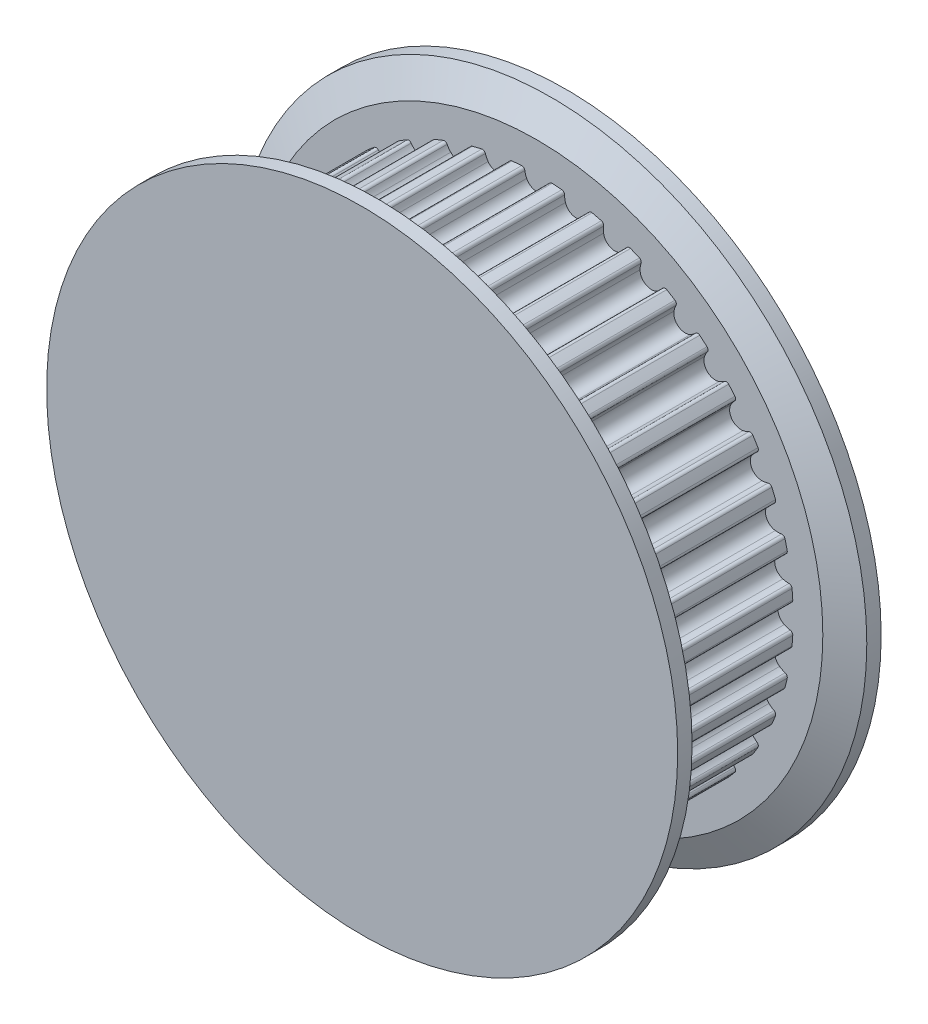
SolidWorks part; units mm, degrees
ref_plane "Front Plane" through (0, 0, 0) normal (0, 0, 1) x (1, 0, 0)
ref_plane "Top Plane" through (0, 0, 0) normal (0, 1, 0) x (1, 0, 0)
ref_plane "Right Plane" through (0, 0, 0) normal (1, 0, 0) x (0, 0, -1)
sketch "Sketch1" plane through (0, 0, 0) normal (0, 0, 1) x (1, 0, 0)
  line L1 (-1.8596, 11.734) -> (1.8596, 11.734) construction
  line L4 (0, 0) -> (0, 11.734) construction
  line L5 (0, 11.734) -> (0, 15.5209) construction
  line L6 (0, 12.738) -> (1.9938, 12.581) construction
  line L7 (1.9938, 12.581) -> (2.8408, 12.4468) construction
  line L8 (1.9938, 12.581) -> (1.8596, 11.734) construction
  line L9 (-1.9938, 12.581) -> (-1.8596, 11.734) construction
  line L10 (-1.9541, 12.3301) -> (-2.4354, 15.367)
  line L11 (-2.4354, 15.367) -> (2.4354, 15.367)
  line L12 (2.4354, 15.367) -> (1.9541, 12.3301)
  circle A0 centre (0, 0) radius 12.738 construction
  circle A1 centre (0, 0) radius 15.367 construction
  circle A2 centre (0, 0) radius 12.484 construction
  arc A3 (-0.4989, 12.0458) -> (0.4989, 12.0458) centre (0, 12.289) ccw
  arc A4 (-0.4989, 12.0458) -> (-0.5887, 12.3344) centre (0.4, 12.484) cw
  arc A5 (-1.9541, 12.3301) -> (-0.746, 12.4617) centre (0, 0) cw
  arc A6 (-0.5887, 12.3344) -> (-0.746, 12.4617) centre (-0.7371, 12.312) ccw
  arc A7 (1.9541, 12.3301) -> (0.746, 12.4617) centre (0, 0) ccw
  arc A8 (0.5887, 12.3344) -> (0.746, 12.4617) centre (0.7371, 12.312) cw
  arc A9 (0.4989, 12.0458) -> (0.5887, 12.3344) centre (-0.4, 12.484) ccw
  point P6 (0, 20.9083)
  point P11 (0, 12.738)
  point P13 (0, 15.367)
  point P14 (0, 12.484)
  dimension "D1" = 5.3874
  dimension "D2" = 2.7829
sketch "Sketch2" plane through (0, 0, 0) normal (1, 0, 0) x (0, 0, -1)
  line L0 (-9.1313, 3.175) -> (9.1313, 3.175)
  line L1 (-9.1313, 3.175) -> (-9.1313, 9.575)
  line L2 (-9.1313, 9.575) -> (-0.7787, 9.575)
  line L3 (-0.7787, 9.575) -> (-0.7787, 15.367)
  line L4 (-0.7787, 15.367) -> (0.6213, 15.367) construction
  line L5 (0.6213, 15.367) -> (0.6213, 12.484) construction
  line L6 (0.6213, 12.484) -> (7.7313, 12.484)
  line L7 (7.7313, 12.484) -> (7.7313, 15.367) construction
  line L8 (7.7313, 15.367) -> (9.1313, 15.367) construction
  line L9 (9.1313, 15.367) -> (9.1313, 3.175)
  line L10 (-9.1313, 0) -> (9.1313, 0) construction
  line L11 (8.4313, 15.367) -> (7.7313, 13.9255)
  line L12 (0.6213, 13.9255) -> (-0.0787, 15.367)
  line L13 (-0.7787, 15.367) -> (-0.0787, 15.367)
  line L14 (0.6213, 13.9255) -> (0.6213, 12.484)
  line L15 (7.7313, 12.484) -> (7.7313, 13.9255)
  line L16 (8.4313, 15.367) -> (9.1313, 15.367)
  arc A0 (0.6213, 13.9255) -> (-0.0787, 15.367) centre (-1.2129, 13.9255) ccw construction
  arc A1 (7.7313, 13.9255) -> (8.4313, 15.367) centre (9.5655, 13.9255) cw construction
  point P12 (0.6213, 13.9255)
  point P14 (-0.0787, 15.367)
  point P20 (7.7313, 13.9255)
  point P21 (8.4313, 15.367)
  point P25 (7.7313, 0)
  point P26 (0.6213, 0)
revolve "Revolve1" add sketch "Sketch2" angle 360 mid plane about L10
sketch "Sketch3" plane through (0, 0, 0) normal (0, 0, 1) x (1, 0, 0)
  line L6 (2.4354, 15.367) -> (-2.4354, 15.367)
  line L7 (1.9541, 12.3301) -> (2.4354, 15.367)
  line L8 (-2.4354, 15.367) -> (-1.9541, 12.3301)
  line L9 (2.4354, 15.367) -> (-2.4354, 15.367)
  line L10 (1.9541, 12.3301) -> (2.4354, 15.367)
  line L11 (-2.4354, 15.367) -> (-1.9541, 12.3301)
  arc A8 (1.9541, 12.3301) -> (0.746, 12.4617) centre (0, 0) ccw
  arc A9 (0.746, 12.4617) -> (0.5887, 12.3344) centre (0.7371, 12.312) ccw
  arc A10 (0.4989, 12.0458) -> (0.5887, 12.3344) centre (-0.4, 12.484) ccw
  arc A11 (-0.4989, 12.0458) -> (0.4989, 12.0458) centre (0, 12.289) ccw
  arc A12 (-0.5887, 12.3344) -> (-0.4989, 12.0458) centre (0.4, 12.484) ccw
  arc A13 (-0.5887, 12.3344) -> (-0.746, 12.4617) centre (-0.7371, 12.312) ccw
  arc A14 (-0.746, 12.4617) -> (-1.9541, 12.3301) centre (0, 0) ccw
  arc A15 (1.9541, 12.3301) -> (0.746, 12.4617) centre (0, 0) ccw
  arc A16 (0.746, 12.4617) -> (0.5887, 12.3344) centre (0.7371, 12.312) ccw
  arc A17 (0.4989, 12.0458) -> (0.5887, 12.3344) centre (-0.4, 12.484) ccw
  arc A18 (-0.4989, 12.0458) -> (0.4989, 12.0458) centre (0, 12.289) ccw
  arc A19 (-0.5887, 12.3344) -> (-0.4989, 12.0458) centre (0.4, 12.484) ccw
  arc A20 (-0.5887, 12.3344) -> (-0.746, 12.4617) centre (-0.7371, 12.312) ccw
  arc A21 (-0.746, 12.4617) -> (-1.9541, 12.3301) centre (0, 0) ccw
  dimension "D1" = 0
extrude "Cut-Extrude1" cut sketch "Sketch3" against normal up to vertex (7.7313 mm away) from vertex up to point (0, 12.484, -7.7313) starting at point (0, 12.484, -0.6213)
pattern_circular "CirPattern1" count 40 over 360 about axis through (0, 0, 9.1313) along (0, 0, 1) of "Cut-Extrude1"
sketch "Sketch4" plane through (0, 0, 0) normal (1, 0, 0) x (0, -1, 0)
  line L0 (0, -0.7787) -> (0, -9.1313) construction
  line L1 (-9.575, -0.7787) -> (9.575, -0.7787) construction
  line L2 (-9.575, -9.1313) -> (9.575, -9.1313) construction
  circle A0 centre (0, -4.955) radius 1.7526
extrude "Cut-Extrude2" cut sketch "Sketch4" along normal through all
ref_plane "Plane1" through (0, 0, 4.955) normal (0, 0, 1) x (1, 0, 0)
sketch "Sketch5" plane through (0, 0, 4.955) normal (0, 0, 1) x (1, 0, 0)
  line L0 (0, 0.1664) -> (0, 9.575) construction
  line L1 (3.175, -1.3716) -> (3.175, 0)
  line L2 (3.556, -1.7526) -> (9.0322, -1.7526)
  line L3 (3.175, 0) -> (9.575, 0) construction
  line L4 (3.175, 0) -> (9.4132, 0)
  line L5 (9.4132, 0) -> (9.4132, -1.3716)
  line L6 (3.556, -1.7526) -> (3.175, -1.3716)
  line L7 (9.4132, -1.3716) -> (9.0322, -1.7526)
  circle A0 centre (0, 0) radius 9.575 construction
  circle A1 centre (0, 0) radius 3.175 construction
  point P2 (3.175, -1.7526)
  point P11 (9.4132, -1.7526)
revolve "Revolve2" add sketch "Sketch5" angle 360 mid plane about L4
sketch "Sketch6" plane through (9.4132, 5.3841, 0) normal (-1, 0, 0) x (0, -1, 0)
  line L1 (5.3841, 5.9669) -> (4.5078, 5.4609)
  line L2 (4.5078, 5.4609) -> (4.5078, 4.4491)
  line L3 (4.5078, 4.4491) -> (5.3841, 3.9431)
  line L4 (5.3841, 3.9431) -> (6.2604, 4.4491)
  line L5 (6.2604, 4.4491) -> (6.2604, 5.4609)
  line L6 (6.2604, 5.4609) -> (5.3841, 5.9669)
  circle A0 centre (5.3841, 4.955) radius 0.8763 construction
  dimension "D1" = 1.7526
extrude "Cut-Extrude3" cut sketch "Sketch6" along normal blind 1.3144
pattern_circular "CirPattern2" count 2 over 90 about axis through (0, 0, 9.1313) along (0, 0, 1) of "Cut-Extrude2", "Revolve2", "Cut-Extrude3"
chamfer "Chamfer1" distance 0.4788 angle 45 2 edges at (3.175, 0, 9.1313) (9.575, 0, 9.1313)
ref_axis "Center Axis 1" through (0, 0, -9.1313) along (0, 0, 1)
ref_plane "Contact Plane 1" through (0, 0, 9.1313) normal (0, 0, 1) x (1, 0, 0)
ref_plane "Contact Plane 2" through (0, 0, -9.1313) normal (0, 0, -1) x (-1, 0, 0)
sketch "Sketch7" plane through (0, 0, 0.7787) normal (0, 0, 1) x (1, 0, 0)
  circle A1 centre (0, 0) radius 15.367
  circle A2 centre (0, 0) radius 15.367
  dimension "D1" = 0
extrude "Cut-Extrude4" cut sketch "Sketch7" along normal through all
sketch "Sketch8" plane through (0, 0, -9.1313) normal (0, 0, -1) x (-1, 0, 0)
  circle A0 centre (0, 0) radius 3.175 construction
  circle A1 centre (0, 0) radius 3.175
extrude "Boss-Extrude1" add sketch "Sketch8" against normal up to surface (9.91 mm away) up to face at (15.367, 0, 0.7787)
equation "\"D2@Sketch1\" = \"D1@Sketch1\"/2"
equation "\"D1@Sketch6\" = \"Set Screw@Sketch4\" / 2"
equation "\"D1@Cut-Extrude3\" = \"D1@Sketch6\"*.75"
equation "\"D1@Chamfer1\"=\"Hub Dia@Sketch2\"*.025"
